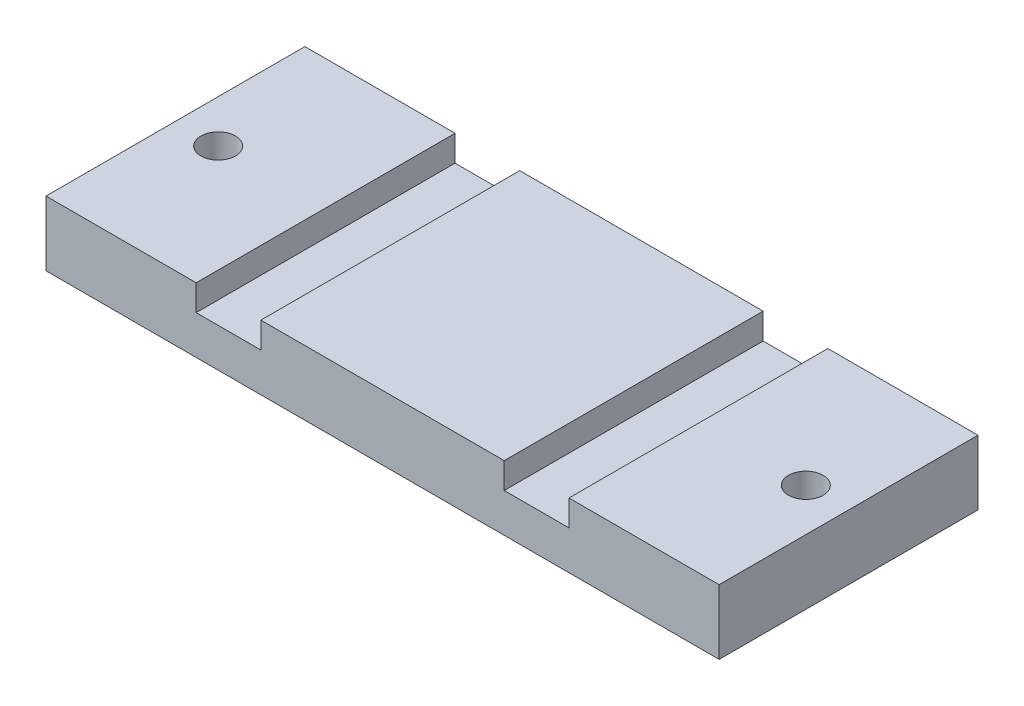
SolidWorks part; units mm, degrees
material "Delrin 2700 NC010, Low Viscosity Acetal Copolymer (SS)"
ref_plane "Front Plane" through (0, 0, 0) normal (0, 0, 1) x (1, 0, 0)
ref_plane "Top Plane" through (0, 0, 0) normal (0, 1, 0) x (1, 0, 0)
ref_plane "Right Plane" through (0, 0, 0) normal (1, 0, 0) x (0, 0, -1)
sketch "Sketch1" plane through (0, 0, 0) normal (0, 1, 0) x (1, 0, 0)
  line L1 (0, 0) -> (66.04, 0)
  line L2 (0, 0) -> (0, 25.4)
  line L3 (0, 25.4) -> (66.04, 25.4)
  line L4 (66.04, 0) -> (66.04, 25.4)
  dimension "D1" = 66.04
  dimension "D2" = 25.4
extrude "Boss-Extrude1" add sketch "Sketch1" along normal blind 6.35
hole_wizard "M3 Clearance Hole1" positions "Sketch4" profile "Sketch3" hole size "M3" standard "ANSI Metric" end condition through all
sketch "Sketch4" plane through (0, 6.35, 0) normal (0, 1, 0) x (1, 0, 0)
  line L0 (0, 12.7) -> (66.04, 12.7) construction
  line L1 (0, 25.4) -> (0, 0) construction
  line L2 (66.04, 0) -> (66.04, 25.4) construction
  line L4 (33.02, 0) -> (33.02, 25.4) construction
  line L5 (0, 0) -> (66.04, 0) construction
  line L6 (66.04, 25.4) -> (0, 25.4) construction
  point P0 (4.191, 12.7)
  point P2 (61.849, 12.7)
  dimension "D1" = 28.829
  dimension "D2" = 28.829
sketch "Sketch3" plane through (4.191, 6.35, -12.7) normal (1, 0, 0) x (0, 0, 1)
  line L0 (0, 0) -> (0, 6.35)
  line L1 (0, 6.35) -> (1.7, 6.35)
  line L2 (1.7, 6.35) -> (1.7, 0)
  line L5 (1.7, 0) -> (0, 0)
  line L11 (0, -6.35) -> (0, 107.95) construction
  dimension "Thru Hole Dia." = 3.4
  dimension "Thru Hole Depth" = 6.35
sketch "Sketch5" plane through (0, 0, 0) normal (0, 0, 1) x (1, 0, 0)
  line L0 (33.02, 6.35) -> (33.02, 0) construction
  line L5 (0, 6.35) -> (66.04, 6.35) construction
  line L6 (0, 0) -> (66.04, 0) construction
  line L7 (51.308, 3.81) -> (44.958, 3.81)
  line L8 (14.732, 6.35) -> (21.082, 6.35)
  line L9 (14.732, 6.35) -> (14.732, 3.81)
  line L10 (14.732, 3.81) -> (21.082, 3.81)
  line L11 (21.082, 6.35) -> (21.082, 3.81)
  line L12 (44.958, 6.35) -> (44.958, 3.81)
  line L13 (51.308, 6.35) -> (44.958, 6.35)
  line L14 (51.308, 6.35) -> (51.308, 3.81)
  dimension "D1" = 6.35
  dimension "D2" = 11.938
  dimension "D3" = 2.54
extrude "Cut-Extrude1" cut sketch "Sketch5" against normal through all
equation "\"spool lenght\"= 45mm"
equation "\"hole distance\"= 0.25in"
equation "\"D2@Sketch4\"=\"spool lenght\"/2 + \"hole distance\""
equation "\"D1@Sketch4\"=\"spool lenght\"/2 + \"hole distance\""
equation "\"tooth clearance\"=0.09"
equation "\"tooth thickness\"= .09"
equation "\"center distance\"= ( 1.42 / 2 ) - 0.2"
equation "\"D2@Sketch5\"=\"center distance\" - 4*\"clearance\""
equation "\"clearance\"= .005"
equation "\"D3@Sketch5\"=\"tooth clearance\" + \"clearance\""
